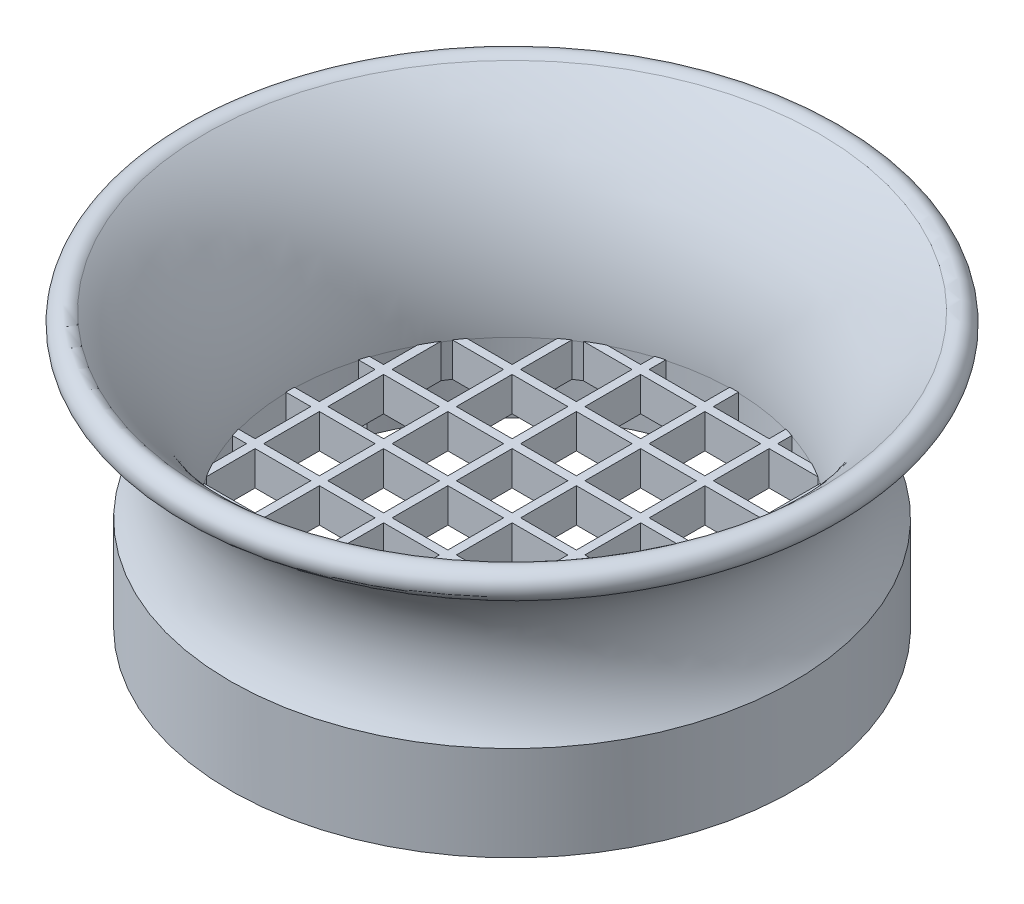
SolidWorks part; units mm, degrees
ref_plane "Front Plane" through (0, 0, 0) normal (0, 0, 1) x (1, 0, 0)
ref_plane "Top Plane" through (0, 0, 0) normal (0, 1, 0) x (1, 0, 0)
ref_plane "Right Plane" through (0, 0, 0) normal (1, 0, 0) x (0, 0, -1)
sketch "Sketch1" plane through (0, 0, 0) normal (0, 0, 1) x (1, 0, 0)
  line L0 (0, 0) -> (0, 84.544) construction
  line L1 (33.02, 0) -> (33.02, 4.9868)
  line L2 (33.02, 0) -> (38.227, 0)
  line L3 (38.227, 0) -> (38.227, -9.0846)
  line L4 (38.227, -9.0846) -> (41.91, -9.0846)
  line L5 (41.91, -9.0846) -> (41.91, 4.9868)
  arc A0 (33.02, 4.9868) -> (45.7065, 31.6876) centre (67.4612, 4.9868) cw
  arc A1 (45.7065, 31.6876) -> (47.8005, 28.2489) centre (46.99, 30.1122) cw
  arc A2 (47.8005, 28.2489) -> (41.91, 4.9868) centre (53.8509, 14.34) ccw
  dimension "D4" = 2.032
  dimension "D8" = 4.9868
  dimension "D1" = 66.04
  dimension "D2" = 76.454
  dimension "D3" = 83.82
  dimension "D5" = 31.6876
  dimension "D6" = 93.98
  dimension "D7" = 53.8509
  dimension "D9" = 9.0846
revolve "Revolve1" add sketch "Sketch1" angle 360 about L0
sketch "Sketch2" plane through (0, -9.0846, 0) normal (0, -1, 0) x (1, 0, 0)
  line L0 (-38.227, 0) -> (-41.8911, -1.2592)
  circle A0 centre (0, 0) radius 38.227 construction
  circle A1 centre (0, 0) radius 41.91 construction
sketch "Sketch3" plane through (0, 0, 0) normal (0, -1, 0) x (1, 0, 0)
  line L0 (0, 0) -> (-76.3593, 0) construction
  line L2 (0, 13.97) -> (-73.1172, 13.97)
  line L3 (0, 13.97) -> (0, -13.97)
  line L4 (0, -13.97) -> (-73.1172, -13.97)
  line L5 (-73.1172, 13.97) -> (-73.1172, -13.97)
  line L6 (0, 13.97) -> (-73.1172, -13.97) construction
  line L7 (0, -13.97) -> (-73.1172, 13.97) construction
  point P3 (-36.5586, 0)
  dimension "D1" = 27.94
  dimension "D2" = 73.1172
extrude "Cut-Extrude2" cut sketch "Sketch3" along normal through all
sketch "Sketch4" plane through (0, 0, 0) normal (0, 1, 0) x (1, 0, 0)
  line L0 (0, 38.227) -> (0, -38.227)
  line L1 (9.5568, 37.0131) -> (9.5568, -37.0131)
  line L2 (19.1135, 33.1056) -> (19.1135, -33.1056)
  line L3 (28.6703, 25.2848) -> (28.6703, -25.2848)
  arc A2 (-35.5829, -13.97) -> (-35.5829, 13.97) centre (0, 0) ccw construction
  dimension "D1" = 38.227
  dimension "D2" = 9.5567
  dimension "D3" = 9.5567
  dimension "D4" = 9.5567
extrude "Extrude-Thin1" add sketch "Sketch4" along normal blind 5.08 thin thin type mid plane wall 1.27
mirror "Mirror1" about plane through (0, 0, 0) normal (1, 0, 0) of "Extrude-Thin1"
pattern_circular "CirPattern1" count 4 over 360 about axis through (0, 0, 0) along (0, -1, 0) of "Mirror1" reverse direction yes
equation "\"D2@Sketch4\"=\"D1@Sketch4\"/4"
equation "\"D3@Sketch4\"=\"D1@Sketch4\"/4"
equation "\"D4@Sketch4\"=\"D1@Sketch4\"/4"
